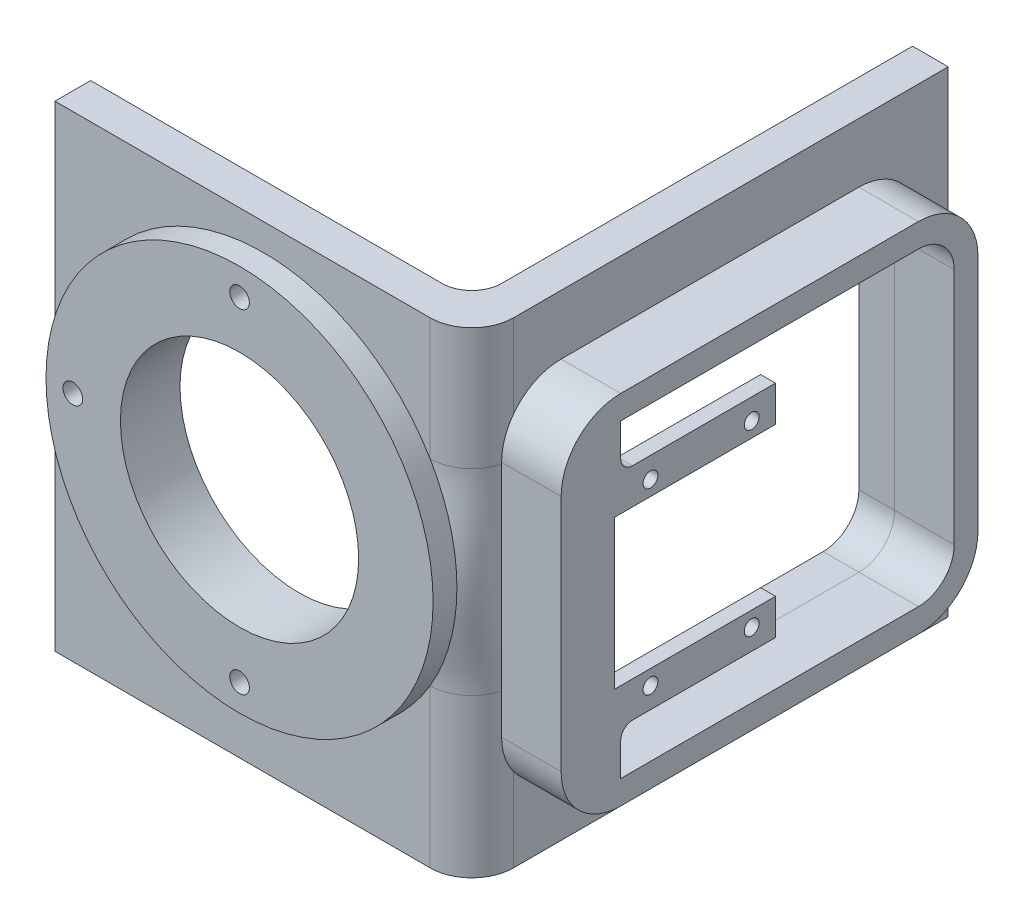
SolidWorks part; units mm, degrees
ref_plane "Front Plane" through (0, 0, 0) normal (0, 0, 1) x (1, 0, 0)
ref_plane "Top Plane" through (0, 0, 0) normal (0, 1, 0) x (1, 0, 0)
ref_plane "Right Plane" through (0, 0, 0) normal (1, 0, 0) x (0, 0, -1)
sketch "Sketch1" plane through (0, 0, 0) normal (0, 0, 1) x (1, 0, 0)
  circle A5 centre (0, 0) radius 32.5
  dimension "D1" = 65
extrude "Boss-Extrude1" add sketch "Sketch1" against normal blind 4
ref_plane "Plane1" through (45, 0, 0) normal (1, 0, 0) x (0, 0, -1)
sketch "Sketch10" plane through (0, 0, -4) normal (0, 0, -1) x (-1, 0, 0)
  line L0 (0, -3) -> (0, 0) construction
  line L1 (-35, -43) -> (35, -43)
  line L2 (-35, -43) -> (-35, 37)
  line L3 (-35, 37) -> (35, 37)
  line L4 (35, -43) -> (35, 37)
  line L5 (-35, -43) -> (35, 37) construction
  line L6 (-35, 37) -> (35, -43) construction
  point P0 (0, -3)
  dimension "D3" = 3
  dimension "D1" = 80
  dimension "D2" = 70
extrude "Boss-Extrude6" add sketch "Sketch10" along normal blind 80
sketch "Sketch2" plane through (45, 0, 0) normal (1, 0, 0) x (0, 0, -1)
  line L2 (0, -3) -> (146.6861, -3) construction
  line L3 (44, -3) -> (44, 30) construction
  line L5 (4, 37) -> (4, -43) construction
  line L6 (84, 37) -> (84, -43) construction
  line L7 (19, -33) -> (69, -33)
  line L8 (9, -23) -> (9, 17)
  line L9 (19, 27) -> (69, 27)
  line L10 (79, -23) -> (79, 17)
  line L11 (9, -33) -> (79, 27) construction
  line L12 (9, 27) -> (79, -33) construction
  arc A1 (19, -33) -> (9, -23) centre (19, -23) cw
  arc A2 (69, -33) -> (79, -23) centre (69, -23) ccw
  arc A3 (69, 27) -> (79, 17) centre (69, 17) cw
  arc A4 (9, 17) -> (19, 27) centre (19, 17) cw
  point P0 (84, -3)
  dimension "D1" = 70
  dimension "D3" = 10
  dimension "D2" = 60
extrude "Boss-Extrude2" add sketch "Sketch2" against normal up to surface (10 mm away) separate body up to face at (35, -3, -44)
sketch "Sketch11" plane through (0, 37, 0) normal (0, 1, 0) x (1, 0, 0)
  line L1 (-35, 84) -> (29, 84)
  line L2 (-35, 84) -> (-35, 10)
  line L3 (-35, 10) -> (29, 10)
  line L4 (29, 84) -> (29, 10)
  dimension "D1" = 74
  dimension "D2" = 64
extrude "Cut-Extrude5" cut sketch "Sketch11" against normal through all
sketch "Sketch4" plane through (35, 0, 0) normal (-1, 0, 0) x (0, 0, 1)
  line L8 (-69, -29) -> (-19, -29)
  line L9 (-75, 17) -> (-75, -23)
  line L10 (-19, 23) -> (-69, 23)
  line L11 (-13, -23) -> (-13, 17)
  line L12 (-69, -29) -> (-19, -29)
  line L13 (-75, 17) -> (-75, -23)
  line L14 (-19, 23) -> (-69, 23)
  line L15 (-13, -23) -> (-13, 17)
  arc A10 (-75, -23) -> (-69, -29) centre (-69, -23) ccw
  arc A11 (-69, 23) -> (-75, 17) centre (-69, 17) ccw
  arc A12 (-13, 17) -> (-19, 23) centre (-19, 17) ccw
  arc A13 (-19, -29) -> (-13, -23) centre (-19, -23) ccw
  arc A14 (-75, -23) -> (-69, -29) centre (-69, -23) ccw
  arc A15 (-69, 23) -> (-75, 17) centre (-69, 17) ccw
  arc A16 (-13, 17) -> (-19, 23) centre (-19, 17) ccw
  arc A17 (-19, -29) -> (-13, -23) centre (-19, -23) ccw
  dimension "D1" = 4
extrude "Cut-Extrude2" cut sketch "Sketch4" against normal through all contours L12 A17 L15 A16 L14 A15 L13 A14 region at (35, -3, -44)
sketch "Sketch5" plane through (45, 0, 0) normal (1, 0, 0) x (0, 0, -1)
  line L0 (48, -3) -> (13, -3) construction
  line L1 (45, 15.5) -> (45, 9.5)
  line L2 (45, 9.5) -> (18, 9.5)
  line L3 (18, 9.5) -> (18, -15.5)
  line L4 (18, -15.5) -> (45, -15.5)
  line L5 (45, -15.5) -> (45, -21.5)
  line L6 (45, -21.5) -> (19, -21.5)
  line L8 (45, 15.5) -> (19, 15.5)
  line L10 (48, -3) -> (48, -18) construction
  line L11 (48, -18) -> (41, -18) construction
  line L12 (41, -18) -> (39, -18) construction
  line L13 (39, -18) -> (24, -18) construction
  line L15 (13, 17) -> (13, -23)
  line L16 (19, 15.5) -> (19, 23)
  line L17 (19, -21.5) -> (19, -29)
  line L18 (13, -23) -> (13, 17) construction
  circle A0 centre (48, -3) radius 11 construction
  arc A1 (19, 23) -> (13, 17) centre (19, 17) ccw construction
  circle A2 centre (41, -18) radius 1.25
  arc A3 (19, 23) -> (13, 17) centre (19, 17) ccw
  circle A6 centre (24, -18) radius 1.25
  circle A7 centre (41, 12) radius 1.25
  circle A9 centre (24, 12) radius 1.25
  arc A10 (13, -23) -> (19, -29) centre (19, -23) ccw
  point P8 (18, -3)
  dimension "D1" = 22
  dimension "D6" = 2.5
  dimension "D3" = 25
  dimension "D4" = 15
  dimension "D5" = 7
  dimension "D7" = 17
  dimension "D9" = 6
  dimension "D10" = 5
  dimension "D12" = 3
  dimension "D2" = 30
extrude "Boss-Extrude3" add sketch "Sketch5" against normal blind 2.5
sketch "Sketch13" plane through (35, 0, 0) normal (1, 0, 0) x (0, 0, -1)
  line L4 (13, 17) -> (13, -23)
  line L5 (19, -29) -> (69, -29)
  line L6 (75, -23) -> (75, 17)
  line L7 (69, 23) -> (19, 23)
  line L8 (13, 17) -> (13, -23)
  line L9 (19, -29) -> (69, -29)
  line L10 (75, -23) -> (75, 17)
  line L11 (69, 23) -> (19, 23)
  arc A6 (19, 23) -> (13, 17) centre (19, 17) ccw
  arc A7 (13, -23) -> (19, -29) centre (19, -23) ccw
  arc A8 (69, -29) -> (75, -23) centre (69, -23) ccw
  arc A9 (75, 17) -> (69, 23) centre (69, 17) ccw
  arc A10 (19, 23) -> (13, 17) centre (19, 17) ccw
  arc A11 (13, -23) -> (19, -29) centre (19, -23) ccw
  arc A12 (69, -29) -> (75, -23) centre (69, -23) ccw
  arc A13 (75, 17) -> (69, 23) centre (69, 17) ccw
  dimension "D1" = 0
extrude "Cut-Extrude6" cut sketch "Sketch13" against normal up to surface (6 mm away) up to face at (29, -3, -47)
sketch "Sketch14" plane through (0, 0, 0) normal (0, 0, 1) x (1, 0, 0)
  circle A2 centre (0, 0) radius 28.5
  circle A3 centre (0, 0) radius 28.5
  dimension "D1" = 4
sketch "Sketch16" plane through (45, 0, 0) normal (1, 0, 0) x (0, 0, -1)
  circle A0 centre (41, -18) radius 2.25
  circle A2 centre (24, -18) radius 2.25
  circle A3 centre (24, 12) radius 2.25
  circle A5 centre (41, 12) radius 2.25
  dimension "D1" = 4.5
extrude "Cut-Extrude8" [suppressed] cut sketch "Sketch16" against normal blind 2.5
fillet "Fillet1" radius 7 1 edges at (35, -3, -4)
fillet "Fillet2" [suppressed] radius 10
sketch "Sketch17" plane through (0, 0, -10) normal (0, 0, -1) x (-1, 0, 0)
  line L0 (-28, 0) -> (0, 0) construction
  line L1 (0, 28) -> (0, 0) construction
  line L2 (28, 0) -> (0, 0) construction
  line L3 (0, -28) -> (0, 0) construction
  circle A0 centre (-28, 0) radius 1.65 construction
  circle A1 centre (0, 28) radius 1.65
  circle A2 centre (28, 0) radius 1.65
  circle A3 centre (0, -28) radius 1.65
  point P10 (0, 0)
  point P17 (0, 0)
  dimension "D4" = 3.3
  dimension "D3" = 28
  dimension "D1" = 4
  dimension "D2" = 4
extrude "Cut-Extrude9" cut sketch "Sketch17" against normal through all
sketch "Sketch19" plane through (29, 0, 0) normal (-1, 0, 0) x (0, 0, 1)
  line L0 (-78, 37) -> (-78, -43) construction
  line L1 (-10, 37) -> (-84, 37) construction
  line L2 (-10, -43) -> (-84, -43) construction
  line L3 (-84, -43) -> (-84, 37) construction
  line L4 (-78, 30) -> (-80, 30)
  line L5 (-78, 30) -> (-78, 25.8)
  line L6 (-78, 25.8) -> (-80, 25.8)
  line L7 (-80, 30) -> (-80, 25.8)
  line L8 (-78, -31.8) -> (-80, -31.8)
  line L9 (-78, -31.8) -> (-78, -36)
  line L10 (-78, -36) -> (-80, -36)
  line L11 (-80, -31.8) -> (-80, -36)
  line L12 (-78, -3) -> (-84, -3) construction
  dimension "D1" = 6
  dimension "D2" = 7
  dimension "D3" = 2
  dimension "D4" = 4.2
extrude "Cut-Extrude10" cut sketch "Sketch19" along direction (1, 0, 0) on the side against the normal blind 4
sketch "Sketch21" plane through (0, 0, -10) normal (0, 0, -1) x (-1, 0, 0)
  line L0 (29, 37) -> (29, -43) construction
  line L1 (31, 30) -> (29, 30)
  line L2 (31, 30) -> (31, 25.8)
  line L3 (31, 25.8) -> (29, 25.8)
  line L4 (29, 30) -> (29, 25.8)
  line L5 (31, -31.8) -> (29, -31.8)
  line L6 (31, -31.8) -> (31, -36)
  line L7 (31, -36) -> (29, -36)
  line L8 (29, -31.8) -> (29, -36)
  line L9 (29, -3) -> (35, -3) construction
  line L10 (35, -43) -> (35, 37) construction
  line L11 (35, 37) -> (-29, 37) construction
  dimension "D1" = 2
  dimension "D2" = 4.2
  dimension "D3" = 7
  dimension "D4" = 6
extrude "Cut-Extrude11" cut sketch "Sketch21" against normal blind 4
sketch "Sketch22" plane through (0, 0, -84) normal (0, 0, -1) x (-1, 0, 0)
  line L0 (-29, 30) -> (-33, 25.8) construction
  line L1 (-29, -31.8) -> (-33, -36) construction
  line L4 (-29, 25.8) -> (-29, 30)
  line L5 (-29, 30) -> (-33, 30)
  line L6 (-33, 30) -> (-33, 25.8)
  line L7 (-33, 25.8) -> (-29, 25.8)
  line L8 (-29, 25.8) -> (-29, 30) construction
  line L9 (-29, 30) -> (-33, 30) construction
  line L11 (-33, 25.8) -> (-29, 25.8) construction
  line L12 (-29, -36) -> (-29, -31.8)
  line L13 (-29, -31.8) -> (-33, -31.8)
  line L14 (-33, -31.8) -> (-33, -36)
  line L15 (-33, -36) -> (-29, -36)
  line L16 (-29, -36) -> (-29, -31.8) construction
  line L17 (-29, -31.8) -> (-33, -31.8) construction
  line L19 (-33, -36) -> (-29, -36) construction
  line L22 (-33, 30) -> (-33, 25.8)
  line L23 (-33, -31.8) -> (-33, -36)
  circle A0 centre (-31, 27.9) radius 1.15
  circle A1 centre (-31, -33.9) radius 1.15
  dimension "D3" = 2.3
  dimension "D1" = 0
  dimension "D2" = 0
extrude "Cut-Extrude12" cut sketch "Sketch22" against normal up to surface (4 mm away) contours A0 | A1 region at (31, 27.9, -84) region at (31, -33.9, -84) up to face at (31, 27.9, -80)
sketch "Sketch23" plane through (-35, 0, 0) normal (-1, 0, 0) x (0, 0, 1)
  line L0 (-10, -36) -> (-6, -31.8) construction
  line L1 (-10, 25.8) -> (-6, 30) construction
  line L4 (-10, -31.8) -> (-10, -36)
  line L5 (-10, -36) -> (-6, -36)
  line L6 (-6, -36) -> (-6, -31.8)
  line L7 (-6, -31.8) -> (-10, -31.8)
  line L8 (-10, -31.8) -> (-10, -36) construction
  line L9 (-10, -36) -> (-6, -36) construction
  line L10 (-6, -36) -> (-6, -31.8) construction
  line L11 (-6, -31.8) -> (-10, -31.8) construction
  line L12 (-10, 30) -> (-10, 25.8)
  line L13 (-10, 25.8) -> (-6, 25.8)
  line L14 (-6, 25.8) -> (-6, 30)
  line L15 (-6, 30) -> (-10, 30)
  line L16 (-10, 30) -> (-10, 25.8) construction
  line L17 (-10, 25.8) -> (-6, 25.8) construction
  line L18 (-6, 25.8) -> (-6, 30) construction
  line L19 (-6, 30) -> (-10, 30) construction
  circle A0 centre (-8, -33.9) radius 1.15
  circle A1 centre (-8, 27.9) radius 1.15
  dimension "D3" = 2.3
  dimension "D1" = 0
  dimension "D2" = 0
extrude "Cut-Extrude13" cut sketch "Sketch23" against normal up to surface (4 mm away) up to face at (-31, -33.9, -8)
sketch "Sketch24" plane through (0, 0, -10) normal (0, 0, -1) x (-1, 0, 0)
  circle A0 centre (0, 0) radius 20
  dimension "D1" = 40
extrude "Cut-Extrude14" cut sketch "Sketch24" against normal up to surface (10 mm away) up to face at (-1.65, 28, 0)
fillet "Fillet4" radius 5 1 edges at (29, -3, -10)
fillet "Fillet5" radius 2 2 edges at (43.75, -21.5, -19) (43.75, 15.5, -19)
